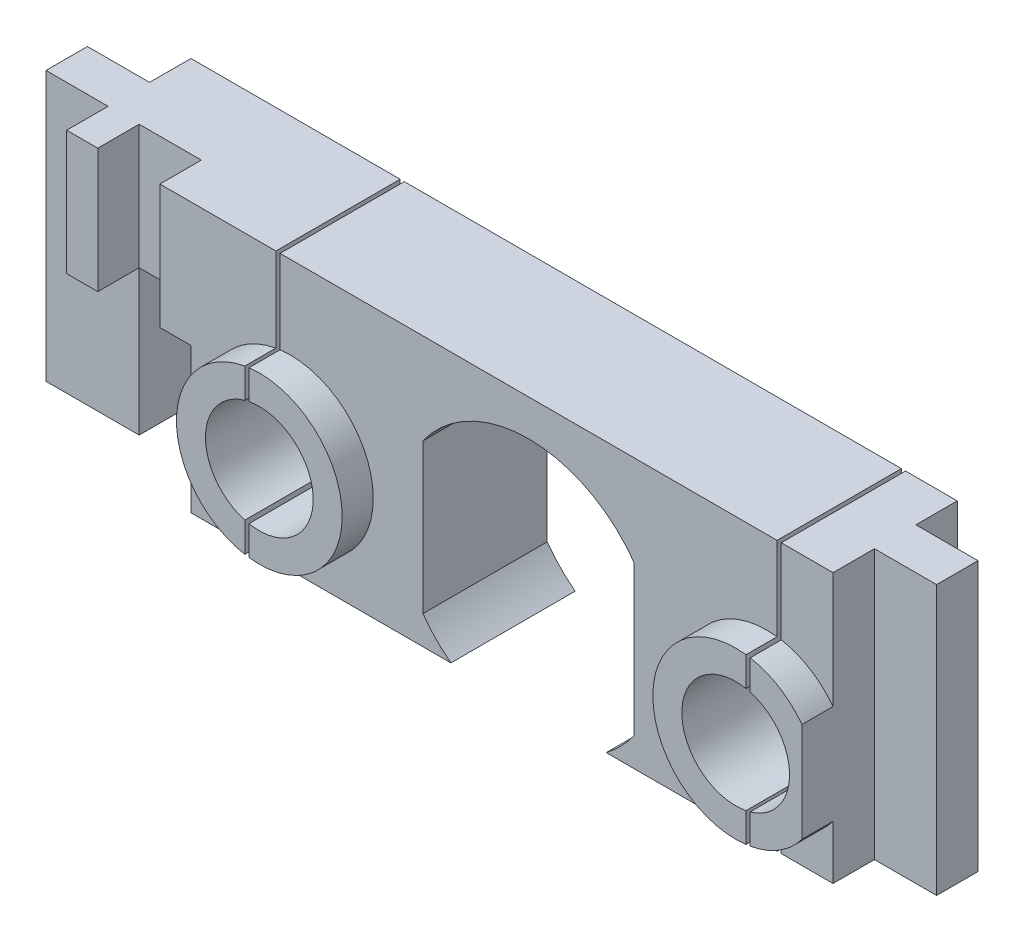
SolidWorks part; units mm, degrees
note: The reader was unsure of these and kept them because the rebuilt part matched: shared geometry of "Sketch16<3>", "Sketch16<4>".
ref_plane "Front Plane" through (0, 0, 0) normal (0, 0, 1) x (1, 0, 0)
ref_plane "Top Plane" through (0, 0, 0) normal (0, 1, 0) x (1, 0, 0)
ref_plane "Right Plane" through (0, 0, 0) normal (1, 0, 0) x (0, 0, -1)
sketch "Sketch1" plane through (0, 0, 0) normal (0, 0, 1) x (1, 0, 0)
  line L0 (-11.5, 0) -> (11.5, 0) construction
  line L1 (3.75, -5) -> (14.7, -5)
  line L2 (-14.7, -5) -> (-3.75, -5)
  line L3 (-14.7, -5) -> (-14.7, 8)
  line L4 (-14.7, 8) -> (14.7, 8)
  line L5 (14.7, -5) -> (14.7, 8)
  line L6 (-17.6832, -10.5909) -> (24.7009, -10.5909)
  line L7 (-24.9768, -7) -> (25.0232, -7) construction
  line L8 (-24.9768, -7) -> (-24.9768, -5) construction
  line L9 (-24.9768, -5) -> (-3.75, -5) construction
  line L10 (25.0232, -7) -> (25.0232, -5) construction
  line L11 (-24.9768, -7) -> (25.0232, -5) construction
  line L12 (-24.9768, -5) -> (25.0232, -7) construction
  line L13 (-5.1, -3.6128) -> (-5.1, 3.6128)
  line L14 (9, -3) -> (14, -3) construction
  line L15 (9, -3) -> (9, 3) construction
  line L16 (9, 3) -> (14, 3) construction
  line L17 (14, -3) -> (14, 3) construction
  line L18 (9, -3) -> (14, 3) construction
  line L19 (9, 3) -> (14, -3) construction
  line L20 (5.1, -3.6128) -> (5.1, 3.6128)
  line L21 (-5.1, -3.6128) -> (5.1, 3.6128) construction
  line L22 (-5.1, 3.6128) -> (5.1, -3.6128) construction
  line L23 (3.75, -5) -> (25.0232, -5) construction
  circle A0 centre (0, 0) radius 2 construction
  circle A1 centre (11.5, 0) radius 9.5 construction
  circle A2 centre (-11.5, 0) radius 9.5 construction
  circle A3 centre (11.5, 0) radius 10.5909 construction
  circle A4 centre (-11.5, 0) radius 10.5909 construction
  circle A5 centre (0, 0) radius 0.5
  circle A6 centre (-11.5, 0) radius 1
  circle A7 centre (11.5, 0) radius 1
  arc A8 (5.1, 3.6128) -> (-5.1, 3.6128) centre (0, 0) ccw
  arc A9 (-5.1, -3.6128) -> (-3.75, -5) centre (0, 0) ccw
  arc A10 (3.75, -5) -> (5.1, -3.6128) centre (0, 0) ccw
  point P13 (0, 0)
  point P17 (0, 8)
  point P18 (0.0232, -6)
  point P29 (3.5089, -10.5909)
  dimension "D1" = 4
  dimension "D2" = 19
  dimension "D5" = 1
  dimension "D6" = 2
  dimension "D9" = 12.5
  dimension "D3" = 13
  dimension "D4" = 2
  dimension "D7" = 5
  dimension "D8" = 6
  dimension "D10" = 10.2
  dimension "D11" = 8
  dimension "D12" = 3.2
extrude "Boss-Extrude1" add sketch "Sketch1" along normal blind 6 contours A10 L1 L5 L4 L3 L2 A9 L13 A8 L20 A7 A6
sketch "Sketch2" plane through (0, 0, 0) normal (0, 0, 1) x (1, 0, 0)
  circle A0 centre (-11.5, 0) radius 2.6
  circle A1 centre (11.5, 0) radius 2.6
  dimension "D1" = 5.2
extrude "Cut-Extrude1" cut sketch "Sketch2" along normal blind 6
sketch "Sketch3" plane through (0, 0, 0) normal (0, 0, 1) x (1, 0, 0)
  line L0 (-14.7, -5) -> (-3.75, -5) construction
  line L1 (-14.7, 8) -> (-22.3, 8)
  line L2 (-14.7, 8) -> (-14.7, -5)
  line L3 (-14.7, -5) -> (-22.3, -5)
  line L4 (-22.3, 8) -> (-22.3, -5)
  dimension "D1" = 7.6
extrude "Boss-Extrude2" add sketch "Sketch3" along normal blind 6
sketch "Sketch6" plane through (0, 0, 0) normal (0, 1, 0) x (1, 0, 0)
  line L0 (-22.3, -6) -> (-22.3, 0) construction
  line L1 (-22.3, -2) -> (-25.3, -2)
  line L2 (-22.3, -2) -> (-22.3, -4)
  line L3 (-22.3, -4) -> (-25.3, -4)
  line L4 (-25.3, -2) -> (-25.3, -4)
  line L5 (14.7, -6) -> (14.7, 0) construction
  line L6 (14.7, -2) -> (17.7, -2)
  line L7 (14.7, -2) -> (14.7, -4)
  line L8 (14.7, -4) -> (17.7, -4)
  line L9 (17.7, -2) -> (17.7, -4)
  point P12 (-22.3, -3)
  point P13 (-22.3, -3)
  dimension "D1" = 2
  dimension "D2" = 3
extrude "Boss-Extrude5" add sketch "Sketch6" along normal up to surface (13 mm away) from surface
sketch "Sketch10" plane through (0, 0, 6) normal (0, 0, 1) x (1, 0, 0)
  line L0 (14.7, 2.4) -> (14.7, -2.4)
  line L2 (14.7, -5) -> (14.7, 8) construction
  circle A0 centre (-11.5, 0) radius 2.6
  circle A1 centre (11.5, 0) radius 2.6
  circle A2 centre (-11.5, 0) radius 2.6 construction
  circle A3 centre (11.5, 0) radius 2.6 construction
  arc A4 (14.7, 2.4) -> (14.7, -2.4) centre (11.5, 0) ccw
  circle A5 centre (-11.5, 0) radius 4
  dimension "D1" = 8
extrude "Boss-Extrude6" add sketch "Sketch10" along normal blind 1.5
sketch "Sketch12" plane through (0, 0, 0) normal (0, 0, -1) x (-1, 0, 0)
  circle A0 centre (-11.5, 0) radius 2.4
  circle A1 centre (11.5, 0) radius 2.4
  circle A2 centre (11.5, 0) radius 2.6
  circle A3 centre (-11.5, 0) radius 2.6
  circle A4 centre (-11.5, 0) radius 2.6 construction
  circle A5 centre (11.5, 0) radius 2.6 construction
  dimension "D1" = 4.8
extrude "Boss-Extrude7" add sketch "Sketch12" against normal blind 2
sketch "Sketch13" plane through (0, -5, 0) normal (0, -1, 0) x (1, 0, 0)
  line L10 (-22.3, 6) -> (-16.3, 6)
  line L11 (-22.3, 6) -> (-3.75, 6) construction
  line L12 (-16.3, 6) -> (-16.3, 4)
  line L13 (-16.3, 4) -> (-17.8, 4)
  line L14 (-17.8, 4) -> (-17.8, 0)
  line L15 (-22.3, 0) -> (-3.75, 0) construction
  line L16 (-17.8, 0) -> (-20.8, 0)
  line L17 (-20.8, 0) -> (-20.8, 4)
  line L18 (-20.8, 4) -> (-22.3, 4)
  line L19 (-22.3, 6) -> (-22.3, 4) construction
  line L20 (-22.3, 4) -> (-22.3, 6)
  dimension "D1" = 2
  dimension "D2" = 6
  dimension "D3" = 3
extrude "Cut-Extrude2" cut sketch "Sketch13" against normal blind 7
sketch "Sketch14" plane through (0, 2, 0) normal (0, -1, 0) x (1, 0, 0)
  line L0 (-16.3, 6) -> (-22.3, 6) construction
  line L1 (-20.8, 4) -> (-17.8, 4)
  line L2 (-20.8, 4) -> (-20.8, 6)
  line L3 (-20.8, 6) -> (-17.8, 6)
  line L4 (-17.8, 4) -> (-17.8, 6)
  line L5 (-17.8, 0) -> (-17.8, 4) construction
extrude "Cut-Extrude3" cut sketch "Sketch14" against normal blind 7
sketch "Sketch15" plane through (0, 0, 0) normal (0, 0, 1) x (1, 0, 0)
  line L0 (-17.8, 8) -> (14.7, 8) construction
  line L1 (-12.2, -5) -> (-12, -5)
  line L2 (-12.2, -5) -> (-12.2, 8)
  line L3 (-12.2, 8) -> (-12, 8)
  line L4 (-12, -5) -> (-12, 8)
  line L5 (-12.2, -5) -> (-12, 8) construction
  line L6 (-12.2, 8) -> (-12, -5) construction
  line L7 (0, 0) -> (0, 6.25) construction
  line L8 (-16.3, -5) -> (-3.75, -5) construction
  line L9 (12.2, 8) -> (12, 8)
  line L10 (12, -5) -> (12, 8)
  line L11 (12.2, -5) -> (12, -5)
  line L12 (12.2, -5) -> (12.2, 8)
  arc A0 (5.1, 3.6128) -> (-5.1, 3.6128) centre (0, 0) ccw construction
  point P0 (-12.1, 1.5)
  dimension "D1" = 0.2
  dimension "D2" = 24
extrude "Cut-Extrude4" cut sketch "Sketch15" against normal mid plane 19
sketch "Sketch16" plane through (-12, 0, 0) normal (-1, 0, 0) x (0, 0, 1)
  line L0 (6, 8) -> (0, 2.3473) construction
  line L1 (4.3, 6.4737) -> (1.7, 6.4737)
  line L2 (4.5, 3.6737) -> (1.5, 3.6737)
  line L3 (4.5, 3.6737) -> (4.5, 6.6737)
  line L4 (4.5, 6.6737) -> (1.5, 6.6737)
  line L5 (1.5, 3.6737) -> (1.5, 6.6737)
  line L6 (4.5, 3.6737) -> (1.5, 6.6737) construction
  line L7 (4.5, 6.6737) -> (1.5, 3.6737) construction
  line L8 (1.7, 3.8737) -> (1.7, 6.4737)
  line L9 (4.3, 3.8737) -> (1.7, 3.8737)
  line L10 (4.3, 3.8737) -> (4.3, 6.4737)
  point P4 (3, 5.1737)
  dimension "D1" = 3
  dimension "D2" = 0.2
extrude "Cut-Extrude5" cut sketch "Sketch16" against normal blind 3 contours L4 L5 L2 L3
mirror "Mirror1" about plane through (0, 0, 0) normal (1, 0, 0) of "Cut-Extrude5"
extrude "Boss-Extrude8" add sketch "Sketch16<3>" against normal blind 3 from surface at 0.2 contours L10 L1 L8 L9 starting at face at (-12.2, -3.4345, 3.875)
sketch "Sketch16<3>" plane through (-12, 0, 0) normal (-1, 0, 0) x (0, 0, 1) same geometry as "Sketch16"
extrude "Boss-Extrude9" add sketch "Sketch16<4>" along normal blind 3 from surface at -24.2 contours L9 L8 L1 L10 starting at face at (12.2, 4.1845, 3.875)
sketch "Sketch16<4>" plane through (-12, 0, 0) normal (-1, 0, 0) x (0, 0, 1) same geometry as "Sketch16"
